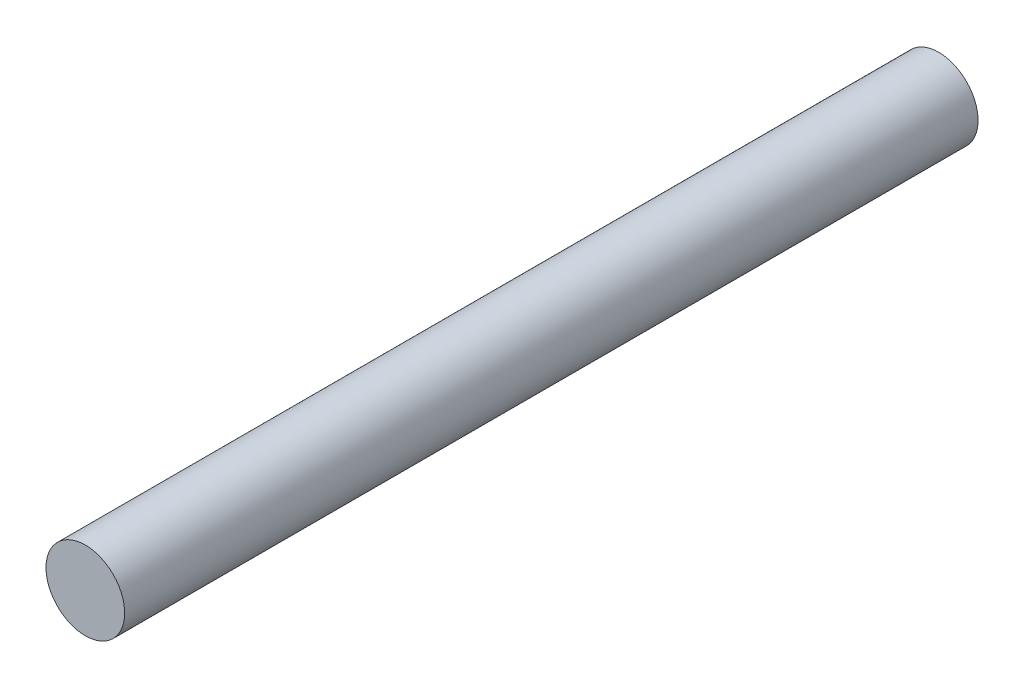
SolidWorks part; units mm, degrees
ref_plane "Alzado" through (0, 0, 0) normal (0, 0, 1) x (1, 0, 0)
ref_plane "Planta" through (0, 0, 0) normal (0, 1, 0) x (1, 0, 0)
ref_plane "Vista lateral" through (0, 0, 0) normal (1, 0, 0) x (0, 0, -1)
sketch "Croquis1" plane through (0, 0, 0) normal (0, 0, 1) x (1, 0, 0)
  circle A0 centre (0, 0) radius 2.475
extrude "Saliente-Extruir1" add sketch "Croquis1" along normal blind 53.7
